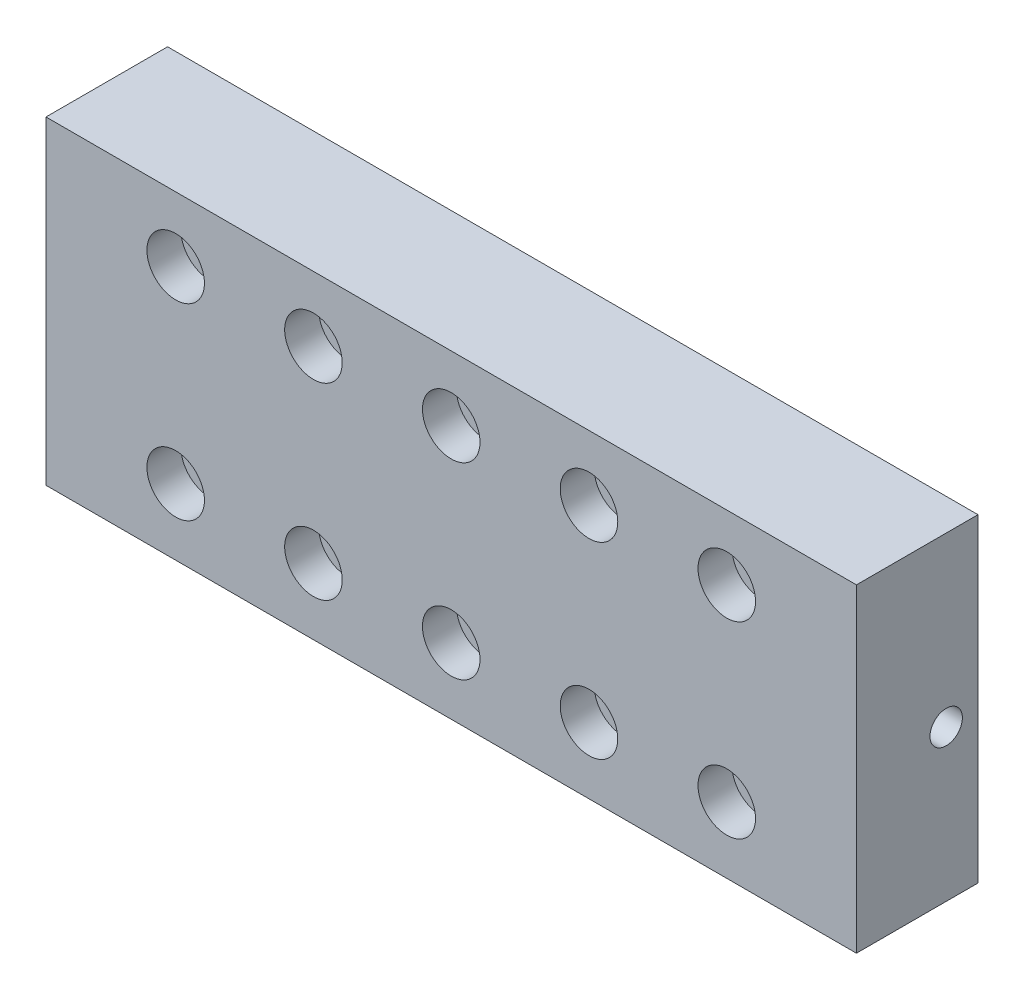
SolidWorks part; units mm, degrees
ref_plane "Ebene vorne" through (0, 0, 0) normal (0, 0, 1) x (1, 0, 0)
ref_plane "Ebene oben" through (0, 0, 0) normal (0, 1, 0) x (1, 0, 0)
ref_plane "Ebene rechts" through (0, 0, 0) normal (1, 0, 0) x (0, 0, -1)
sketch "Skizze2" plane through (0, 0, 0) normal (0, 0, 1) x (1, 0, 0)
  line L1 (0, 0) -> (100, 0)
  line L2 (0, 0) -> (0, 39.3642)
  line L3 (0, 39.3642) -> (100, 39.3642)
  line L4 (100, 0) -> (100, 39.3642)
  dimension "D1" = 39.3642
  dimension "D2" = 100
extrude "Aufsatz-Linear austragen1" add sketch "Skizze2" along normal blind 30
sketch "Skizze3" plane through (0, 0, 30) normal (0, 0, 1) x (1, 0, 0)
  line L0 (0, 19.6821) -> (100, 19.6821) construction
  line L1 (0, 39.3642) -> (0, 0) construction
  line L2 (100, 0) -> (100, 39.3642) construction
ref_plane "Ebene2" through (0, 19.7642, 0) normal (0, 1, 0) x (1, 0, 0)
sketch "Skizze9" plane through (0, 0, 30) normal (0, 0, 1) x (1, 0, 0)
  line L0 (50, 0) -> (50, 39.3642) construction
  line L1 (0, 0) -> (100, 0) construction
  line L2 (100, 39.3642) -> (0, 39.3642) construction
ref_plane "Ebene3" through (50, 0, 0) normal (-1, 0, 0) x (0, 0, 1)
sketch "Skizze10" plane through (50, 0, 0) normal (-1, 0, 0) x (0, 0, 1)
  line L0 (14.9458, 42.0451) -> (14.9458, -1.991) construction
  line L1 (-1.6741, 19.9497) -> (31.3778, 19.9497) construction
  circle A0 centre (14.9458, 20.027) radius 5
  dimension "D1" = 10
extrude "Schnitt-Linear austragen1" cut sketch "Skizze10" against normal blind 40 and the other way blind 40
ref_plane "Ebene4" through (90, 0, 0) normal (-1, 0, 0) x (0, 0, 1)
ref_plane "Ebene5" through (10, 0, 0) normal (-1, 0, 0) x (0, 0, 1)
sketch "Skizze17" plane through (90, 0, 0) normal (-1, 0, 0) x (0, 0, 1)
  circle A0 centre (14.9458, 20.027) radius 1.5
  dimension "D1" = 3
extrude "Schnitt-Linear austragen2" cut sketch "Skizze17" against normal blind 5
mirror "Spiegeln1" about plane through (50, 0, 0) normal (-1, 0, 0) of "Schnitt-Linear austragen2"
sketch "Skizze18" plane through (0, 39.3642, 0) normal (0, 1, 0) x (1, 0, 0)
  line L0 (100, -15) -> (0, -15) construction
  line L1 (100, -30) -> (100, 0) construction
ref_plane "Ebene6" through (0, 0, 15) normal (0, 0, -1) x (-1, 0, 0)
sketch "Skizze24" plane through (0, 0, 30) normal (0, 0, 1) x (1, 0, 0)
  line L0 (0, 39.3642) -> (0, 0) construction
  line L1 (100, 39.3642) -> (0, 39.3642) construction
  line L4 (100, 0) -> (100, 39.3642) construction
  circle A0 centre (16, 31.3642) radius 2.05
  circle A1 centre (33, 31.3642) radius 2.05
  circle A2 centre (50, 31.3642) radius 2.05
  circle A3 centre (67, 31.3642) radius 2.05
  circle A4 centre (84, 31.3642) radius 2.05
  dimension "D1" = 4.1
  dimension "D4" = 4.1
  dimension "D5" = 4.1
  dimension "D6" = 4.1
  dimension "D7" = 4.1
  dimension "D2" = 16
  dimension "D3" = 8
  dimension "D8" = 17
  dimension "D9" = 17
  dimension "D10" = 17
  dimension "D11" = 17
  dimension "D12" = 16
extrude "Schnitt-Linear austragen4" cut sketch "Skizze24" against normal through all
mirror "Spiegeln4" about plane through (0, 19.7642, 0) normal (0, 1, 0) of "Schnitt-Linear austragen4"
sketch "Skizze41" plane through (0, 0, 30) normal (0, 0, 1) x (1, 0, 0)
  circle A0 centre (16, 31.3642) radius 3.55
  dimension "D1" = 7.1
extrude "Schnitt-Linear austragen11" cut sketch "Skizze41" against normal blind 4.2
pattern_linear "Lineares Muster5" count 5 spacing 17 along (1, 0, 0) of "Schnitt-Linear austragen11"
mirror "Spiegeln9" about plane through (0, 19.7642, 0) normal (0, 1, 0) of "Lineares Muster5"
sketch "Skizze28" plane through (0, 0, 0) normal (0, -1, 0) x (-1, 0, 0)
  line L4 (-12.45, -6.7653) -> (-19.55, -6.7653)
  line L5 (-12.45, -6.7653) -> (-12.45, -10.0653)
  line L6 (-12.45, -10.0653) -> (-19.55, -10.0653)
  line L7 (-19.55, -6.7653) -> (-19.55, -10.0653)
  point P3 (-16, -2)
  point P7 (-16, -6.7653)
  dimension "D1" = 7.1
  dimension "D2" = 3.55
  dimension "D3" = 3.3
  dimension "D4" = 7.1
extrude "Schnitt-Linear austragen5" cut sketch "Skizze28" against normal blind 7.96
sketch "Skizze22" plane through (0, 0, 0) normal (-1, 0, 0) x (0, 0, 1)
  line L0 (30, 39.3642) -> (0, 39.3642) construction
  line L1 (0, 0) -> (15, 0)
  line L2 (0, 0) -> (0, 39.3642)
  line L3 (0, 39.3642) -> (15, 39.3642)
sketch "Skizze32" plane through (100, 0, 0) normal (1, 0, 0) x (0, 0, -1)
  line L0 (-8.4153, 7.96) -> (-8.4153, 0) construction
  line L1 (-6.7653, 7.96) -> (-10.0653, 7.96) construction
  line L2 (-30, 0) -> (0, 0) construction
  line L3 (-8.4153, 0) -> (-8.4153, 41.7817) construction
ref_plane "Ebene7" through (0, 0, 8.4) normal (0, 0, -1) x (-1, 0, 0)
sketch "Skizze33" plane through (0, 0, 8.4) normal (0, 0, -1) x (-1, 0, 0)
  line L0 (-16, 8.1642) -> (-16, 39.3642) construction
  line L1 (-100, 39.3642) -> (0, 39.3642) construction
  line L2 (-16, 39.3642) -> (-16, 0) construction
  line L3 (0, 0) -> (-100, 0) construction
ref_plane "Ebene8" through (16, 0, 0) normal (-1, 0, 0) x (0, 0, 1)
sketch "Skizze34" plane through (0, 0, 8.4) normal (0, 0, -1) x (-1, 0, 0)
  line L1 (-16, 12.2056) -> (-19.5, 10.1849)
  line L2 (-19.5, 10.1849) -> (-19.5, 6.1434)
  line L3 (-19.5, 6.1434) -> (-16, 4.1227)
  line L4 (-16, 4.1227) -> (-12.5, 6.1434)
  line L5 (-12.5, 6.1434) -> (-12.5, 10.1849)
  line L6 (-12.5, 10.1849) -> (-16, 12.2056)
  circle A0 centre (-16, 8.1642) radius 3.5 construction
  dimension "D1" = 7
extrude "Schnitt-Linear austragen8" cut sketch "Skizze34" against normal blind 4.2 and the other way blind 1.65
pattern_linear "Lineares Muster3" count 5 spacing 17 along (1, 0, 0) of "Schnitt-Linear austragen8"
pattern_linear "Lineares Muster4" count 5 spacing 17 along (1, 0, 0) of "Schnitt-Linear austragen5"
mirror "Spiegeln6" about plane through (0, 19.7642, 0) normal (0, 1, 0) of "Schnitt-Linear austragen8"
mirror "Spiegeln7" about plane through (0, 19.7642, 0) normal (0, 1, 0) of "Lineares Muster3"
mirror "Spiegeln8" about plane through (0, 19.7642, 0) normal (0, 1, 0) of "Lineares Muster4"
sketch "Skizze35" plane through (0, 0, 30) normal (0, 0, 1) x (1, 0, 0)
  line L0 (89.9018, 21.3451) -> (89.9018, 39.3769) construction
  line L1 (89.9018, 39.3769) -> (89.9018, 0) construction
  line L2 (0, 0) -> (100, 0) construction
ref_plane "Ebene9" through (90, 0, 0) normal (1, 0, 0) x (0, 0, -1)
sketch "Skizze36" plane through (90, 0, 0) normal (1, 0, 0) x (0, 0, -1)
  line L0 (-20.1004, 18.2046) -> (-18.9246, 18.6336)
  circle A0 centre (-18.9246, 18.6336) radius 0.75
  point P3 (-19.5125, 18.4191)
  point P4 (-18.9246, 18.6336)
  dimension "D1" = 1.5
sketch "Skizze37" plane through (100, 0, 0) normal (1, 0, 0) x (0, 0, -1)
  circle A0 centre (-18.9246, 18.6336) radius 0.7369
extrude "Schnitt-Linear austragen9" cut sketch "Skizze37" against normal through all
sketch "Skizze40" plane through (100, 0, 0) normal (1, 0, 0) x (0, 0, -1)
  circle A0 centre (-18.9246, 18.6336) radius 2
  dimension "D1" = 4
extrude "Schnitt-Linear austragen10" cut sketch "Skizze40" against normal blind 6
sketch "Skizze42" plane through (0, 0, 0) normal (-1, 0, 0) x (0, 0, 1)
  line L0 (10.1439, 18.6336) -> (10.8642, 18.8426) construction
  circle A0 centre (14.9458, 20.027) radius 5 construction
  circle A1 centre (10.8642, 18.8426) radius 0.75
  dimension "D1" = 0.75
extrude "Schnitt-Linear austragen12" cut sketch "Skizze42" against normal blind 10
fillet "Verrundung1" radius 1 1 edges at (94, 18.6336, 18.1877)
fillet "Verrundung2" radius 1 1 edges at (90, 18.6336, 19.6615)
sketch "Skizze45" plane through (100, 0, 0) normal (1, 0, 0) x (0, 0, -1)
  line L1 (-15, 39.3642) -> (0, 39.3642)
  line L2 (-15, 39.3642) -> (-15, 0)
  line L3 (-15, 0) -> (0, 0)
  line L4 (0, 39.3642) -> (0, 0)
extrude "Schnitt-Linear austragen14" cut sketch "Skizze45" against normal blind 100
